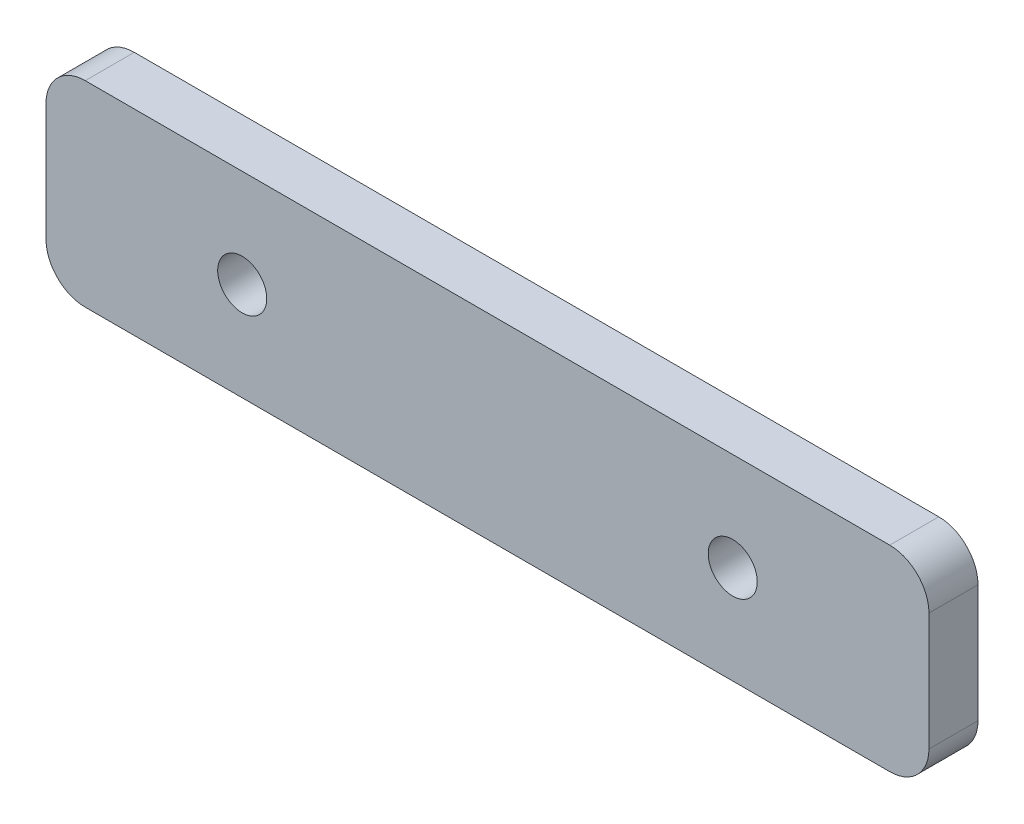
SolidWorks part; units mm, degrees
material "1060 Alloy"
ref_plane "Front Plane" through (0, 0, 0) normal (0, 0, 1) x (1, 0, 0)
ref_plane "Top Plane" through (0, 0, 0) normal (0, 1, 0) x (1, 0, 0)
ref_plane "Right Plane" through (0, 0, 0) normal (1, 0, 0) x (0, 0, -1)
sketch "Sketch1" plane through (0, 0, 0) normal (0, 0, 1) x (1, 0, 0)
  line L1 (-28.575, -6.35) -> (28.575, -6.35)
  line L2 (-28.575, -6.35) -> (-28.575, 6.35)
  line L3 (-28.575, 6.35) -> (28.575, 6.35)
  line L4 (28.575, -6.35) -> (28.575, 6.35)
  line L5 (-28.575, -6.35) -> (28.575, 6.35) construction
  line L6 (-28.575, 6.35) -> (28.575, -6.35) construction
  circle A0 centre (-15.875, 0) radius 1.5875
  circle A1 centre (15.875, 0) radius 1.5875
  point P0 (0, 0)
  point P6 (0, 0)
  point P7 (-28.575, 0)
  point P12 (28.575, 0)
  dimension "D3" = 3.175
  dimension "D4" = 3.175
  dimension "D6" = 12.7
  dimension "D1" = 12.7
  dimension "D2" = 57.15
  dimension "D5" = 12.7
extrude "Boss-Extrude1" add sketch "Sketch1" along normal blind 3.175
fillet "Fillet1" radius 2.54 4 edges at (28.575, -6.35, 1.5875) (-28.575, -6.35, 1.5875) (28.575, 6.35, 1.5875) (-28.575, 6.35, 1.5875)
